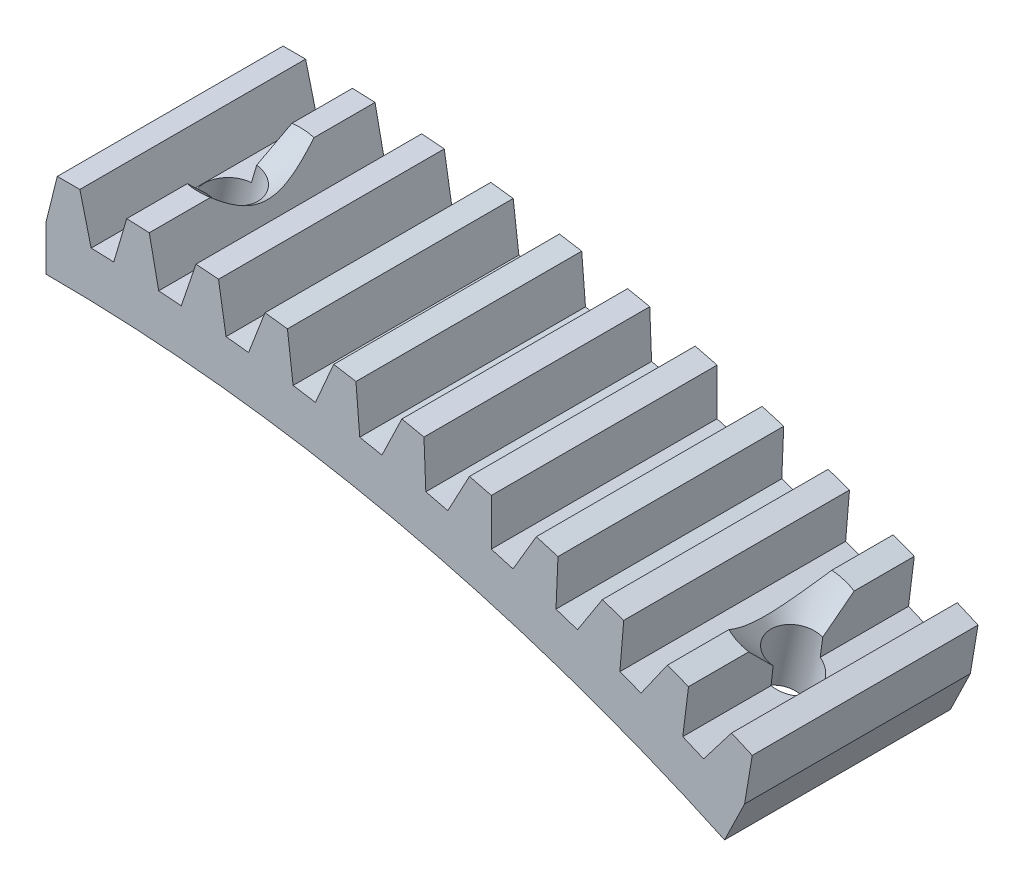
SolidWorks part; units mm, degrees
ref_plane "Front Plane" through (0, 0, 0) normal (0, 0, 1) x (1, 0, 0)
ref_plane "Top Plane" through (0, 0, 0) normal (0, 1, 0) x (1, 0, 0)
ref_plane "Right Plane" through (0, 0, 0) normal (1, 0, 0) x (0, 0, -1)
sketch "Sketch1" plane through (0, 0, 0) normal (0, 0, 1) x (1, 0, 0)
  line L0 (1.27, 190.5) -> (0, 185.42)
  line L1 (1.27, 190.5) -> (3.81, 190.5)
  line L2 (3.81, 190.5) -> (5.08, 185.42)
  line L3 (0, 185.42) -> (0, 180.34)
  line L4 (7.874, 185.3224) -> (0, 0) construction
  line L5 (7.874, 185.3224) -> (7.6554, 180.1774)
  line L6 (0, 0) -> (0, 75.3052) construction
  circle A0 centre (0, 0) radius 180.34 construction
  arc A1 (0, 180.34) -> (7.6554, 180.1774) centre (0, 0) cw
  arc A2 (5.08, 185.42) -> (7.874, 185.3224) centre (0, 0) cw
  dimension "D5" = 360.68
  dimension "D1" = 2.54
  dimension "D2" = 5.08
  dimension "D3" = 5.08
  dimension "D4" = 5.08
  dimension "D6" = 2.794
extrude "Boss-Extrude1" add sketch "Sketch1" along normal blind 25.4
ref_axis "Axis1" through (0, 0, 26.67) along (0, 0, -1)
pattern_circular "CirPattern2" count 11 every 2.35 about axis through (0, 0, 26.67) along (0, 0, -1) of "Boss-Extrude1"
sketch "Sketch4" plane through (0, 0, 25.4) normal (0, 0, 1) x (1, 0, 0)
  line L0 (81.1181, 166.812) -> (78.8661, 162.181)
  line L1 (78.5947, 168.0156) -> (79.4557, 173.1807) construction
  line L2 (78.5947, 168.0156) -> (76.3424, 163.384)
  arc A0 (81.1181, 166.812) -> (78.5947, 168.0156) centre (0, 0) ccw
  circle A1 centre (0, 0) radius 180.34 construction
  arc A2 (76.3424, 163.384) -> (78.8661, 162.181) centre (0, 0) cw
  arc M1 (0, 180.34) -> (78.8661, 162.181) centre (0, 0) cw
  line M2 (78.8661, 162.181) -> (81.1181, 166.812)
  arc M3 (81.1181, 166.812) -> (78.5947, 168.0156) centre (0, 0) ccw
extrude "Cut-Extrude2" cut sketch "Sketch4" against normal blind 25.4 contours L2 M3 M1 M2 region at (78.7319, 165.1014, 25.4)
ref_plane "Plane1" through (38.1712, 171.862, 0) normal (-0.2168, -0.9762, 0) x (-0.9762, 0.2168, 0)
sketch "Sketch7" plane through (38.1712, 171.862, 0) normal (-0.2168, -0.9762, 0) x (-0.9762, 0.2168, 0)
  line L0 (-39.1014, 0) -> (-39.1014, -25.4) construction
  line L1 (-40.2959, -25.4) -> (-40.2959, 0) construction
  line L2 (40.2028, -25.4) -> (40.2028, 0) construction
  circle A0 centre (-14.8959, -12.7) radius 2.3813
  circle A1 centre (14.8028, -12.7) radius 2.3813
  point P0 (-14.8959, -12.7)
  point P2 (14.8028, -12.7)
  point P6 (-39.1014, -12.7)
  dimension "D3" = 4.7625
  dimension "D1" = 25.4
  dimension "D2" = 25.4
ref_plane "Plane2" through (40.8037, 183.7144, 0) normal (0.2168, 0.9762, 0) x (-0.9762, 0.2168, 0)
sketch "Sketch9" plane through (40.8037, 183.7144, 0) normal (0.2168, 0.9762, 0) x (-0.9762, 0.2168, 0)
  line L0 (-32.3443, 25.4) -> (-32.3443, 0) construction
  line L1 (32.3941, 25.4) -> (32.3941, 0) construction
  circle A0 centre (-32.3443, 12.7) radius 3.3729
  circle A1 centre (32.3941, 12.7) radius 3.3729
  point P0 (-32.3443, 12.7)
  point P4 (32.3941, 12.7)
hole_wizard "CSK for #10 Flat Head Machine Screw (100)1" positions "Sketch9" profile "Sketch10" countersink size "#10" standard "ANSI Inch" end condition through all
sketch "Sketch10" plane through (72.3785, 176.7015, 12.7) normal (0, 0, 1) x (-0.9762, 0.2168, 0)
  line L0 (0, 0) -> (0, 28.6938)
  line L1 (0, 28.6938) -> (2.8067, 28.6938)
  line L2 (2.8067, 28.6938) -> (2.8067, 3.5433)
  line L3 (2.8067, 3.5433) -> (6.35, 0)
  line L5 (6.35, 0) -> (0, 0)
  line L6 (-2.8067, 3.5433) -> (-6.35, 0) construction
  line L11 (0, -6.35) -> (0, 107.95) construction
  dimension "Thru Hole Dia." = 5.6134
  dimension "Thru Hole Depth" = 28.6938
  dimension "Near C'Sink Dia." = 12.7
  dimension "Near C'Sink Angle" = 90
sketch "Sketch5" plane through (0, 0, 0) normal (0, 1, 0) x (1, 0, 0)
  line L0 (79.4557, -25.4) -> (79.4557, 0) construction
  line L1 (0, -25.4) -> (0, 0) construction
  circle A0 centre (17.78, -12.7) radius 2.3813 construction
  circle A1 centre (61.6757, -12.7) radius 2.3813 construction
  point P0 (17.78, -12.7)
  point P2 (61.6757, -12.7)
  point P8 (79.4557, -12.7)
  dimension "D1" = 4.7625
  dimension "D2" = 17.78
  dimension "D3" = 17.78
